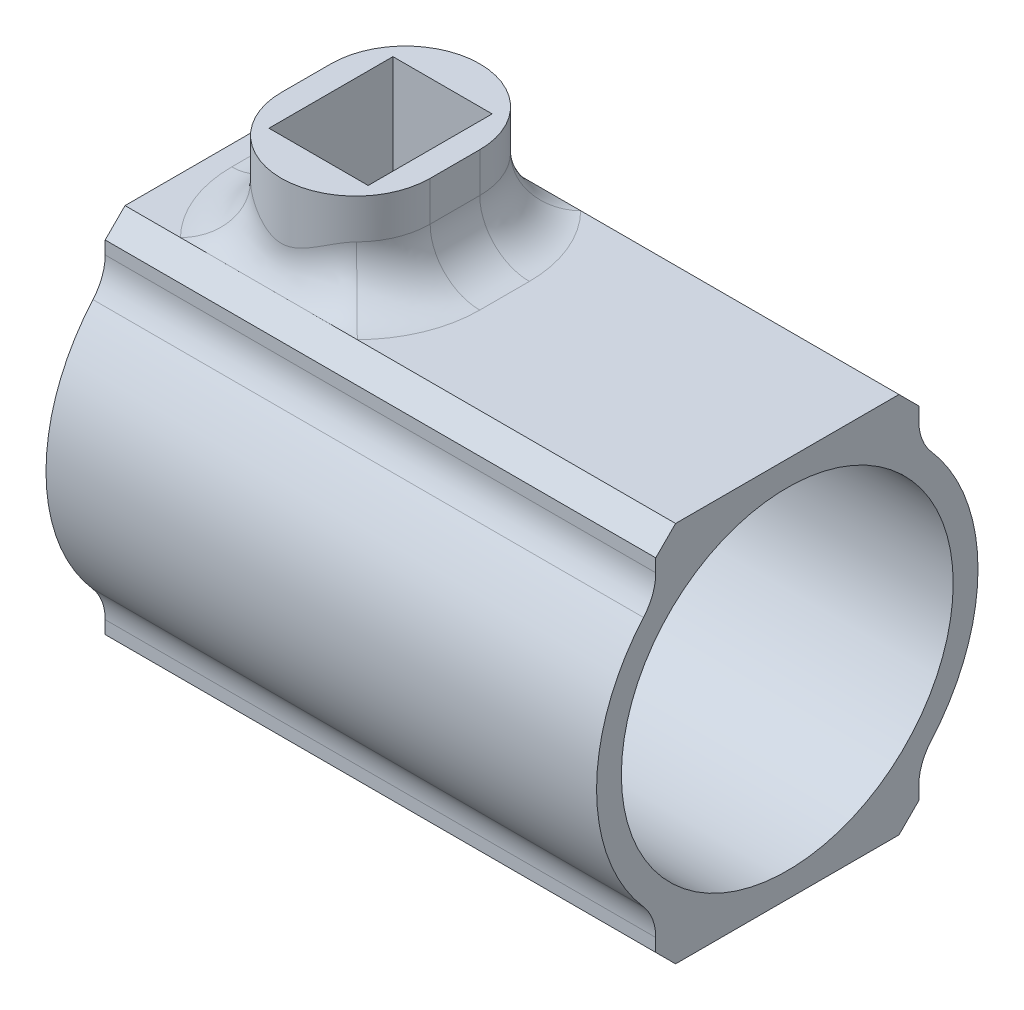
SolidWorks part; units mm, degrees
ref_plane "Front Plane" through (0, 0, 0) normal (0, 0, 1) x (1, 0, 0)
ref_plane "Top Plane" through (0, 0, 0) normal (0, 1, 0) x (1, 0, 0)
ref_plane "Right Plane" through (0, 0, 0) normal (1, 0, 0) x (0, 0, -1)
sketch "Sketch1" plane through (0, 0, 0) normal (1, 0, 0) x (0, 0, -1)
  circle A0 centre (0, 0) radius 38.45
  dimension "D1" = 76.9
extrude "Boss-Extrude1" add sketch "Sketch1" along normal mid plane 111
shell "Shell1" thickness 5 removed face at (55.5, 0, -38.45)
ref_plane "Plane1" through (0, 38.45, 0) normal (0, 1, 0) x (1, 0, 0)
sketch "Sketch2" plane through (0, 38.45, 0) normal (0, 1, 0) x (1, 0, 0)
  line L0 (-55.5, 38.45) -> (-55.5, -38.45) construction
  line L1 (-55.5, 26.52) -> (55.5, 26.52)
  line L2 (-55.5, 26.52) -> (-55.5, -26.52)
  line L3 (-55.5, -26.52) -> (55.5, -26.52)
  line L4 (55.5, 26.52) -> (55.5, -26.52)
  line L5 (55.5, -38.45) -> (55.5, 38.45) construction
  point P8 (55.5, 0)
  dimension "D1" = 53.04
extrude "Boss-Extrude2" add sketch "Sketch2" against normal up to surface (10.6095 mm away) up to face at (55.5, 0, -38.45)
mirror "Mirror1" about plane through (0, 0, 0) normal (0, 1, 0) of "Boss-Extrude2"
sketch "Sketch3" plane through (0, 38.45, 0) normal (0, 1, 0) x (1, 0, 0)
  line L0 (-50.5, 26.52) -> (-50.5, -26.52) construction
  line L1 (55.5, 26.52) -> (-55.5, 26.52) construction
  line L2 (-55.5, -26.52) -> (55.5, -26.52) construction
  line L3 (-55.5, 26.52) -> (-55.5, -26.52) construction
  line L5 (-36.5, 12.5) -> (-16.5, 12.5)
  line L6 (-36.5, 12.5) -> (-36.5, -12.5)
  line L7 (-36.5, -12.5) -> (-16.5, -12.5)
  line L8 (-16.5, 12.5) -> (-16.5, -12.5)
  point P12 (-16.5, 0)
  dimension "D1" = 5
  dimension "D2" = 14
  dimension "D3" = 25
  dimension "D4" = 20
extrude "Cut-Extrude1" cut sketch "Sketch3" against normal up to next
ref_plane "Plane2" through (0, 38.55, 0) normal (0, 1, 0) x (1, 0, 0)
sketch "Sketch5" plane through (0, 38.45, 0) normal (0, 1, 0) x (1, 0, 0)
  line L0 (-26.5, 5) -> (-26.5, -5) construction
  line L1 (-11.5, 5) -> (-11.5, -5)
  line L2 (-41.5, 5) -> (-41.5, -5)
  line L3 (-26.5, 20) -> (-26.5, -20) construction
  line L4 (-36.5, 0) -> (-16.5, 0) construction
  line L5 (-36.5, 12.5) -> (-36.5, -12.5) construction
  line L6 (-16.5, 12.5) -> (-16.5, -12.5) construction
  arc A0 (-11.5, 5) -> (-41.5, 5) centre (-26.5, 5) ccw
  arc A1 (-41.5, -5) -> (-11.5, -5) centre (-26.5, -5) ccw
  point P2 (-26.5, 0)
  dimension "D1" = 30
  dimension "D2" = 40
extrude "Boss-Extrude5" add sketch "Sketch5" along normal blind 18
sketch "Sketch6" plane through (0, 56.45, 0) normal (0, 1, 0) x (1, 0, 0)
  line L4 (-16.5, 12.5) -> (-36.5, 12.5)
  line L5 (-16.5, -12.5) -> (-16.5, 12.5)
  line L6 (-36.5, -12.5) -> (-16.5, -12.5)
  line L7 (-36.5, 12.5) -> (-36.5, -12.5)
  line L8 (-16.5, 12.5) -> (-36.5, 12.5)
  line L9 (-16.5, -12.5) -> (-16.5, 12.5)
  line L10 (-36.5, -12.5) -> (-16.5, -12.5)
  line L11 (-36.5, 12.5) -> (-36.5, -12.5)
  dimension "D1" = 0
extrude "Cut-Extrude2" cut sketch "Sketch6" against normal up to next
sketch "Sketch7" plane through (0, 38.45, 0) normal (0, 1, 0) x (1, 0, 0)
  line L0 (55.5, 38.45) -> (-55.5, 38.45) construction
  line L1 (-11.5, 38.45) -> (55.5, 38.45)
  line L2 (-11.5, 38.45) -> (-11.5, -38.45)
  line L3 (-11.5, -38.45) -> (55.5, -38.45)
  line L4 (55.5, 38.45) -> (55.5, -38.45)
  line L5 (-11.5, -5) -> (-11.5, 5) construction
chamfer "Chamfer1" distance 4 angle 45 4 edges at (0, -38.45, 26.52) (0, -38.45, -26.52) (0, 38.45, 26.52) (0, 38.45, -26.52)
fillet "Fillet1" radius 10 4 edges at (0, 27.8405, -26.52) (0, 27.8405, 26.52) (0, -27.8405, 26.52) (0, -27.8405, -26.52)
fillet "Fillet2" radius 10 4 edges at (-26.5, 38.45, 20) (-41.5, 38.45, 0) (-26.5, 38.45, -20) (-11.5, 38.45, 0)
sketch "Sketch8" plane through (-55.5, 0, 0) normal (-1, 0, 0) x (0, 0, 1)
  circle A0 centre (0, 10) radius 2.5
  circle A1 centre (0, 0) radius 10 construction
  circle A2 centre (0, 0) radius 10 construction
  circle A3 centre (8.6603, -5) radius 2.5
  circle A4 centre (0, 0) radius 10 construction
  circle A5 centre (-8.6603, -5) radius 2.5
  dimension "D1" = 5
  dimension "D2" = 10
  dimension "D3" = 3
extrude "Cut-Extrude4" cut sketch "Sketch8" against normal up to next
equation "\"Can Daimeter\"= 66.3"
equation "\"Can Height\"= 121.6"
equation "\"Bottom of hole to Can bottome\"= 14"
equation "\"D1@Sketch1\"=\"Can Daimeter\"+0.6 +\"Shell Thickness\"*2"
equation "\"Shell Thickness\"= 5"
equation "\"Bottom To flat\"= 106"
equation "\"D1@Boss-Extrude1\"=\"Bottom To flat\"+\"Shell Thickness\""
equation "\"D1@Shell1\"=\"Shell Thickness\""
equation "\"D1@Sketch2\"=\"Can Daimeter\"*0.8"
equation "\"D1@Sketch3\"=\"Shell Thickness\""
equation "\"D2@Sketch3\"=14"
equation "\"Hole Length\"= 25"
equation "\"Hole Height\"= 20"
equation "\"D3@Sketch3\"=\"Hole Length\""
equation "\"D4@Sketch3\"=\"Hole Height\""
equation "\"D1@Sketch5\"=\"Hole Height\"+10"
equation "\"D2@Sketch5\"=\"Hole Length\"+15"
